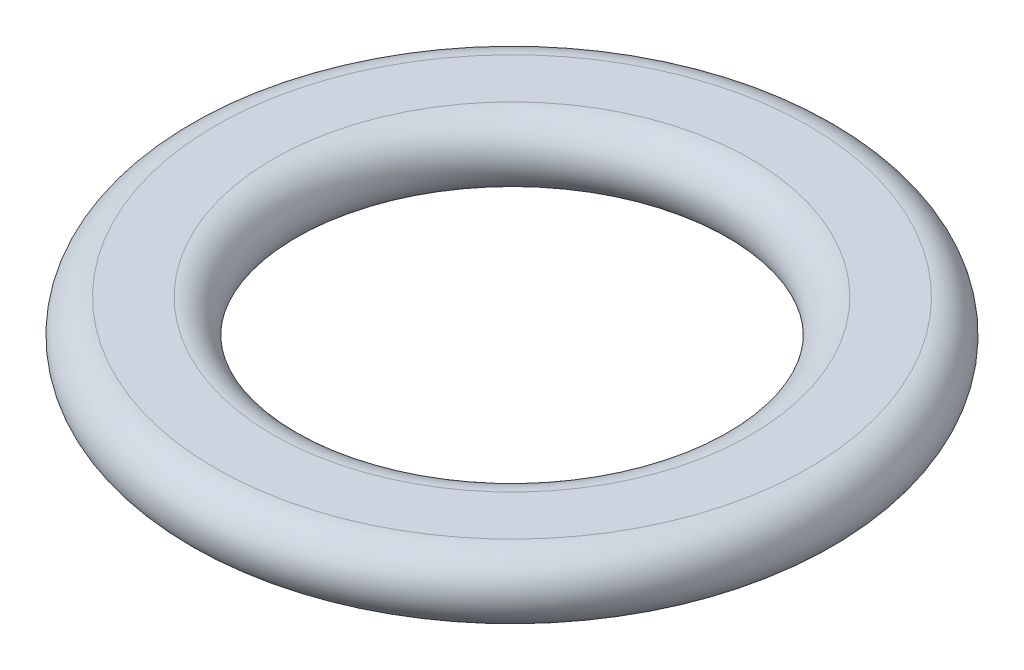
SolidWorks part; units mm, degrees
material "Silicon Rubber"
ref_plane "Front Plane" through (0, 0, 0) normal (0, 0, 1) x (1, 0, 0)
ref_plane "Top Plane" through (0, 0, 0) normal (0, 1, 0) x (1, 0, 0)
ref_plane "Right Plane" through (0, 0, 0) normal (1, 0, 0) x (0, 0, -1)
ref_axis "CentralAxis" through (0, 0.715, 0) along (0, -1, 0)
sketch "ProfileS" plane through (0, 0, 0) normal (0, 0, 1) x (1, 0, 0)
  line L0 (2.9, 0) -> (3.6, 0) construction
  line L1 (2.9, 0.4) -> (3.6, 0.4)
  line L2 (2.9, -0.4) -> (3.6, -0.4)
  line L3 (0, 0.4) -> (0, -0.4) construction
  arc A0 (2.9, 0.4) -> (2.9, -0.4) centre (2.9, 0) ccw
  arc A1 (3.6, -0.4) -> (3.6, 0.4) centre (3.6, 0) ccw
  point P2 (3.25, 0)
  point P8 (2.5, 0)
  point P9 (4, 0)
  dimension "Height" = 0.8
  dimension "ID" = 5
  dimension "OD" = 8
revolve "Profile" add sketch "ProfileS" angle 360 about L3
